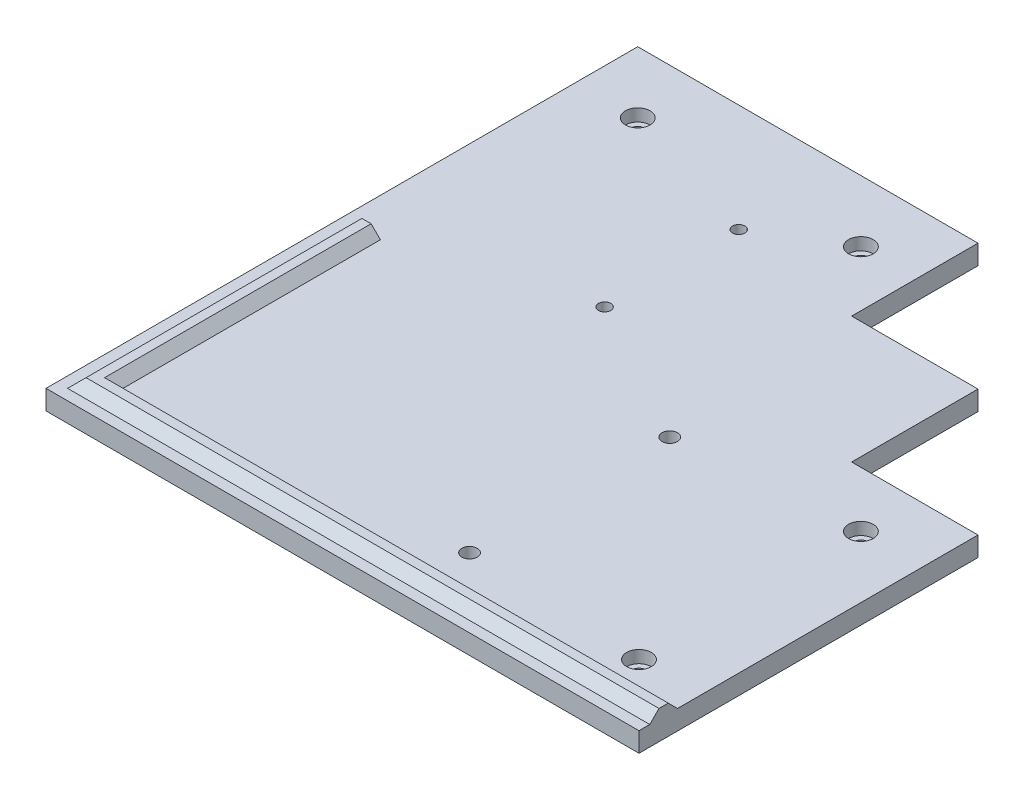
SolidWorks part; units mm, degrees
ref_plane "Front Plane" through (0, 0, 0) normal (0, 0, 1) x (1, 0, 0)
ref_plane "Top Plane" through (0, 0, 0) normal (0, 1, 0) x (1, 0, 0)
ref_plane "Right Plane" through (0, 0, 0) normal (1, 0, 0) x (0, 0, -1)
sketch "Sketch1" plane through (0, 0, 0) normal (0, 1, 0) x (1, 0, 0)
  line L1 (-96.2, 96) -> (96.2, 96)
  line L2 (-96.2, 96) -> (-96.2, -96)
  line L3 (-96.2, -96) -> (96.2, -96)
  line L4 (96.2, 96) -> (96.2, -96)
  line L5 (-96.2, 96) -> (96.2, -96) construction
  line L6 (-96.2, -96) -> (96.2, 96) construction
  point P0 (0, 0)
  dimension "D1" = 192
  dimension "D2" = 192.4
extrude "Boss-Extrude1" add sketch "Sketch1" along normal blind 6.35
sketch "Sketch2" plane through (0, 6.35, 0) normal (0, 1, 0) x (1, 0, 0)
  line L1 (-96.2, 96) -> (-55.2, 96)
  line L2 (-96.2, 96) -> (-96.2, 55)
  line L3 (-96.2, 55) -> (-55.2, 55) construction
  line L4 (-55.2, 96) -> (-55.2, 55) construction
  line L5 (-96.2, 55) -> (-55.2, 55)
  line L6 (-96.2, 55) -> (-96.2, 14)
  line L7 (-96.2, 14) -> (-55.2, 14)
  line L8 (-55.2, 55) -> (-55.2, 14)
  line L9 (-55.2, 96) -> (-14.2, 96)
  line L10 (-55.2, 96) -> (-55.2, 55)
  line L11 (-55.2, 55) -> (-14.2, 55)
  line L12 (-14.2, 96) -> (-14.2, 55)
  line M14 (96.2, 96) -> (-96.2, 96)
  line M15 (-96.2, 96) -> (-96.2, -96)
  dimension "D1" = 41
extrude "Cut-Extrude1" cut sketch "Sketch2" against normal up to next contours L8 L5 L7 M15 | L10 L5 M14 M15 | L12 L10 L11 M14 region at (-75.7, 6.35, -75.5) region at (-34.7, 6.35, -75.5) region at (-75.7, 6.35, -34.5)
sketch "Sketch3" plane through (0, 6.35, 0) normal (0, 1, 0) x (1, 0, 0)
  line L0 (-96.2, 76) -> (96.2, 76) construction
  line L1 (-96.2, 96) -> (-56.2, 96) construction
  line L2 (-96.2, 96) -> (-96.2, -96) construction
  line L3 (-96.2, -96) -> (-56.2, -96) construction
  line L4 (96.2, 96) -> (-96.2, 96)
  line L5 (96.2, -96) -> (96.2, 96)
  line L6 (-96.2, -96) -> (96.2, -96)
  line L7 (-96.2, 96) -> (-96.2, -96)
  line L8 (96.2, 96) -> (-96.2, 96) construction
  line L9 (96.2, -96) -> (96.2, 96) construction
  line L10 (-96.2, -96) -> (96.2, -96) construction
  line L11 (-96.2, 96) -> (-96.2, -96) construction
  line L12 (-56.2, 96) -> (-56.2, -96) construction
  line L13 (-96.2, 96) -> (96.2, 96) construction
  line L14 (-96.2, 96) -> (-96.2, 56) construction
  line L15 (-96.2, 56) -> (96.2, 56) construction
  line L16 (96.2, 96) -> (96.2, 56) construction
  line L17 (-76.2, 96) -> (-76.2, -96) construction
  point P20 (-76.2, -4)
  point P22 (-76.2, -76)
  point P24 (3.8, 76)
  point P26 (76.2, 76)
  dimension "D2" = 40
  dimension "D3" = 40
  dimension "D4" = 20
  dimension "D5" = 60
  dimension "D6" = 60
  dimension "D7" = 20
  dimension "D8" = 20
  dimension "D1" = 0
hole_wizard "CBORE for M4 SHCS1" positions "Sketch3" profile "Sketch4" counterbore size "M4" standard "ANSI Metric" end condition up to next
sketch "Sketch4" plane through (76.2, 6.35, -76) normal (1, 0, 0) x (0, 0, 1)
  line L0 (0, 0) -> (0, 6.35)
  line L1 (0, 6.35) -> (2.25, 6.35)
  line L3 (2.25, 6.35) -> (2.25, 4)
  line L4 (2.25, 4) -> (4, 4)
  line L5 (4, 4) -> (4, 0)
  line L7 (4, 0) -> (0, 0)
  line L11 (0, -6.35) -> (0, 107.95) construction
  dimension "Thru Hole Dia." = 4.5
  dimension "Thru Hole Depth" = 6.35
  dimension "C'Bore Dia." = 8
  dimension "C'Bore Depth" = 4
mirror "Mirror1" [suppressed] of bodies 105
delete or keep bodies "Body-Delete/Keep 1" [suppressed] type delete bodies bodies 105
mirror "Mirror2" [suppressed] of bodies 108
delete or keep bodies "Body-Delete/Keep 2" [suppressed] type delete bodies bodies 108
sketch "Sketch5" plane through (0, 6.35, 0) normal (0, 1, 0) x (1, 0, 0)
  line L0 (-18.7, -8.525) -> (-18.7, -73.475) construction
  line L1 (-56.2, -4.375) -> (18.8, -4.375) construction
  line L2 (-56.2, -4.375) -> (-56.2, -77.625) construction
  line L3 (-56.2, -77.625) -> (18.8, -77.625) construction
  line L4 (18.8, -4.375) -> (18.8, -77.625) construction
  line L5 (-96.2, -41) -> (96.2, -41) construction
  line L6 (-96.2, 14) -> (-96.2, -96) construction
  line L7 (96.2, -96) -> (96.2, 96) construction
  line L8 (-56.2, -41) -> (18.8, -41) construction
  circle A0 centre (-18.7, -8.525) radius 2.5
  circle A1 centre (-18.7, -73.475) radius 2.5
  point P12 (-18.7, -41)
  point P15 (-18.7, -41)
  dimension "D4" = 5
  dimension "D1" = 73.25
  dimension "D2" = 75
  dimension "D3" = 40
  dimension "D5" = 64.95
extrude "Cut-Extrude2" cut sketch "Sketch5" against normal blind 6
sketch "Sketch6" plane through (0, 0.35, 0) normal (0, 1, 0) x (1, 0, 0)
  circle A0 centre (-18.7, -8.525) radius 2.25
  circle A1 centre (-18.7, -73.475) radius 2.25
  dimension "D1" = 4.5
extrude "Cut-Extrude3" cut sketch "Sketch6" against normal up to next
sketch "Sketch7" plane through (0, 6.35, 0) normal (0, 1, 0) x (1, 0, 0)
  line L0 (96.2, -96) -> (96.2, 96) construction
  line L1 (28.45, 61) -> (163.95, 61) construction
  line L2 (28.45, 61) -> (28.45, 17.5) construction
  line L3 (28.45, 17.5) -> (163.95, 17.5) construction
  line L4 (163.95, 61) -> (163.95, 17.5) construction
  line L5 (28.45, 61) -> (163.95, 17.5) construction
  line L6 (28.45, 17.5) -> (163.95, 61) construction
  line L7 (96.2, 96) -> (-14.2, 96) construction
  circle A0 centre (28.45, 61) radius 1.75
  circle A1 centre (28.45, 17.5) radius 1.75
  point P0 (96.2, 39.25)
  dimension "D4" = 3.5
  dimension "D1" = 43.5
  dimension "D2" = 135.5
  dimension "D3" = 35
extrude "Cut-Extrude4" cut sketch "Sketch7" against normal up to next
sketch "Sketch8" plane through (0, 6.35, 0) normal (0, 1, 0) x (1, 0, 0)
  circle A0 centre (28.45, 61) radius 2
  circle A1 centre (28.45, 17.5) radius 2
  dimension "D1" = 4
extrude "Cut-Extrude5" cut sketch "Sketch8" against normal blind 5
sketch "Sketch9" plane through (0, 6.35, 0) normal (0, 1, 0) x (1, 0, 0)
  line L2 (0, 0) -> (96.2, 0) construction
  line L3 (96.2, -96) -> (96.2, 96) construction
  line L4 (-96.2, -88) -> (88.2, -88)
  line L5 (88.2, -88) -> (88.2, 96)
  line L6 (-96.2, -88) -> (88.2, -88)
  line L7 (88.2, -88) -> (88.2, 0)
  dimension "D1" = 8
extrude "Extrude-Thin1" add sketch "Sketch9" along normal blind 3 thin thin type mid plane wall 3
chamfer "Chamfer1" distance 3 angle 45 4 edges at (-4.75, 6.35, 86.5) (86.7, 6.35, 43.25) (-3.25, 6.35, 89.5) (89.7, 6.35, 44.75)
mirror "Mirror3" about plane through (96.2, 6.35, -96) normal (-1, 0, 0) of bodies 115 113
delete or keep bodies "Body-Delete/Keep 4" type delete bodies bodies 115
equation "\"D2@Sketch1\"=384.8/2"
